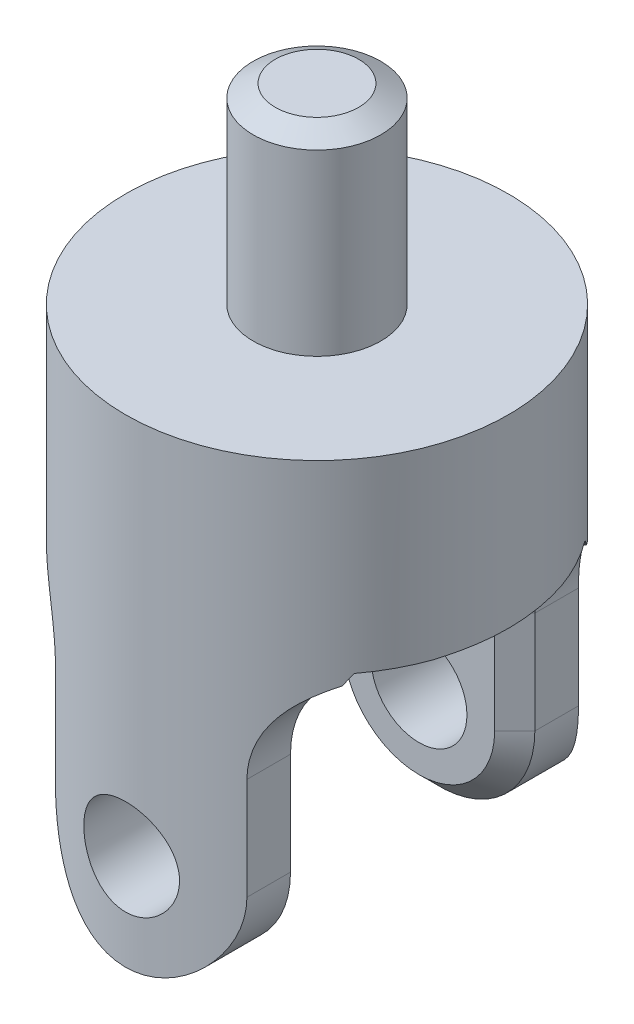
SolidWorks part; units mm, degrees
note: '?' marks a value the reader was unsure of.
ref_plane "Front" through (0, 0, 0) normal (0, 0, 1) x (1, 0, 0)
ref_plane "Top" through (0, 0, 0) normal (0, 1, 0) x (-1, 0, 0)
ref_plane "Right" through (0, 0, 0) normal (1, 0, 0) x (0, 0, -1)
sketch "Sketch1" plane through (0, 0, 0) normal (0, 1, 0) x (-1, 0, 0)
  circle A0 centre (0, 0) radius 19.05
  dimension "D1" = 38.1
extrude "Base-Extrude" add sketch "Sketch1" along normal blind 47.625
sketch "Sketch2" plane through (0, 0, 0) normal (0, 0, 1) x (1, 0, 0)
  line L0 (0, 0) -> (0, 23.7435) construction
  line L1 (9.525, 9.525) -> (9.525, 19.685)
  line L2 (-9.525, 9.525) -> (-9.525, 19.685)
  line L3 (19.05, 29.21) -> (19.05, -1.3662)
  line L4 (19.05, -1.3662) -> (-19.05, -1.3662)
  line L5 (-19.05, -1.3662) -> (-19.05, 29.21)
  line L6 (19.05, 0) -> (-19.05, 0) construction
  arc A0 (-9.525, 9.525) -> (9.525, 9.525) centre (0, 9.525) ccw
  arc A1 (9.525, 19.685) -> (19.05, 29.21) centre (19.05, 19.685) cw
  arc A2 (-9.525, 19.685) -> (-19.05, 29.21) centre (-19.05, 19.685) ccw
  dimension "D3" = 9.525
  dimension "D1" = 38.1
  dimension "D2" = 19.05
  dimension "D4" = 29.21
extrude "Cut-Extrude1" cut sketch "Sketch2" against normal through all and the other way through all
sketch "Sketch8" plane through (0, 0, 0) normal (1, 0, 0) x (0, 0, -1)
  line L0 (-10.16, -7.4553) -> (10.16, -7.4553)
  line L1 (-10.16, -7.4553) -> (-10.16, 29.1452)
  line L2 (10.16, 29.1452) -> (-10.16, 29.1452)
  line L3 (10.16, 29.1452) -> (10.16, -7.4553)
  point P4 (0, 0)
  dimension "D1" = 10.16
  dimension "D2" = 20.32
extrude "Cut-Extrude5" cut sketch "Sketch8" against normal through all and the other way blind 47.625
sketch "Sketch11" plane through (0, 0, 0) normal (0, 0, 1) x (1, 0, 0)
  circle A0 centre (0, 9.525) radius 4.7625
  dimension "D1" = 9.525
extrude "Cut-Extrude6" cut sketch "Sketch11" against normal through all and the other way through all
sketch "Sketch12" plane through (0, 47.625, 0) normal (0, 1, 0) x (-1, 0, 0)
  circle A0 centre (0, 0) radius 6.35
  dimension "D1" = 12.7
extrude "Boss-Extrude1" add sketch "Sketch12" along normal blind 19.05
chamfer "Chamfer3" distance 1.27 angle 60 1 edges at (0, 66.675, 6.35) first distance on face at (0, 66.675, 6.35)
ref_axis "Axis1" through (0, 97.625, 0) along (0, -1, 0)?
sketch "Sketch13" plane through (0, 66.675, 0) normal (0, 1, 0) x (-1, 0, 0)
  line L0 (-4.7625, 4.2001) -> (-4.7625, -4.2001)
  circle A0 centre (0, 0) radius 6.35 construction
  arc A1 (-4.7625, 4.2001) -> (-4.7625, -4.2001) centre (0, 0) ccw
  dimension "D1" = 1.5875
extrude "Cut-Extrude7" [suppressed] cut sketch "Sketch13" against normal blind 12.7
chamfer "Chamfer4" distance 2 angle 45 10 edges at (-11.3465, 25.287, -10.16) (-9.525, 14.605, -10.16) (0, 0, -10.16) (9.525, 14.605, -10.16) (11.3465, 25.287, -10.16) (-11.3465, 25.287, 10.16) (-9.525, 14.605, 10.16) (0, 0, 10.16) (9.525, 14.605, 10.16) (11.3465, 25.287, 10.16)
